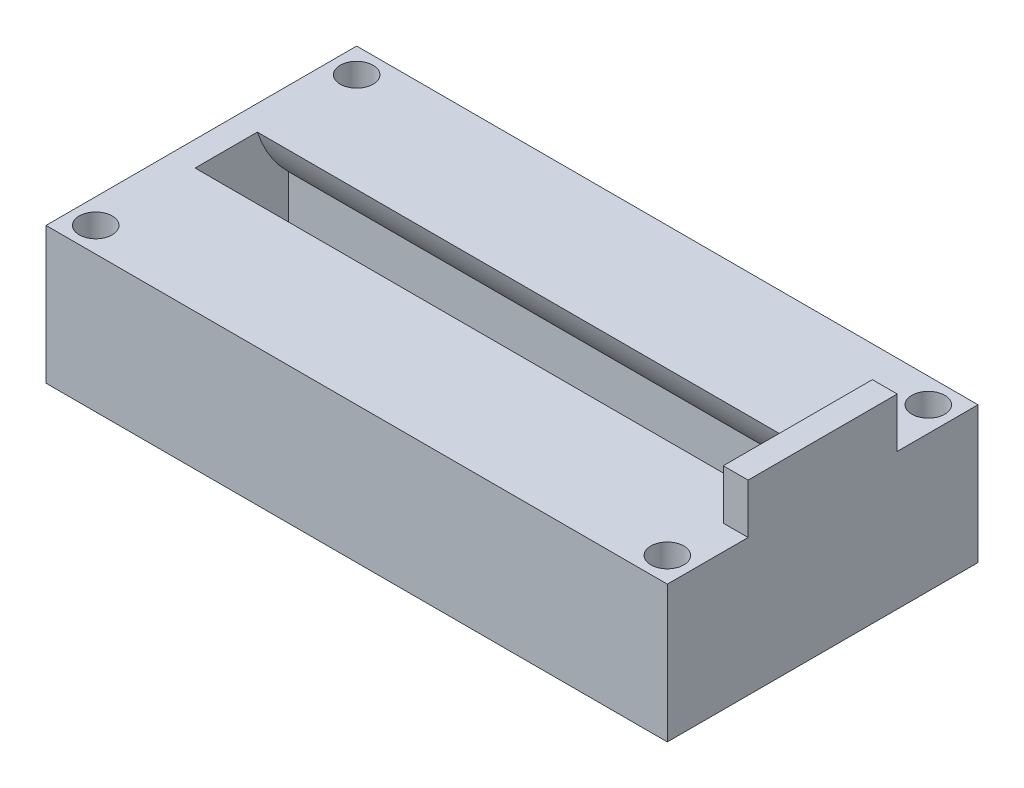
SolidWorks part; units mm, degrees
ref_plane "Front Plane" through (0, 0, 0) normal (0, 0, 1) x (1, 0, 0)
ref_plane "Top Plane" through (0, 0, 0) normal (0, 1, 0) x (1, 0, 0)
ref_plane "Right Plane" through (0, 0, 0) normal (1, 0, 0) x (0, 0, -1)
sketch "Sketch1" plane through (0, 0, 0) normal (0, 1, 0) x (1, 0, 0)
  line L0 (25, 22.1808) -> (25, 21.9237) construction
  line L1 (0, 0) -> (50, 0)
  line L2 (0, 0) -> (0, 25)
  line L4 (50, 0) -> (50, 25)
  line L8 (0, 25) -> (50, 25)
  line L18 (2, 17.5) -> (48, 17.5)
  line L19 (2, 17.5) -> (2, 7.5)
  line L20 (2, 7.5) -> (48, 7.5)
  line L21 (48, 17.5) -> (48, 7.5)
  circle A0 centre (2, 23) radius 1.325
  circle A1 centre (48, 23) radius 1.325
  circle A2 centre (48, 2) radius 1.325
  circle A3 centre (2, 2) radius 1.325
  point P5 (0, 0)
  dimension "D6" = 2.65
  dimension "D7" = 2.65
  dimension "D8" = 2.65
  dimension "D9" = 2.65
  dimension "D18" = 2
  dimension "D19" = 7.5
  dimension "D1" = 50
  dimension "D2" = 25
  dimension "D3" = 10
  dimension "D4" = 25
  dimension "D5" = 46
  dimension "D10" = 2
  dimension "D11" = 2
  dimension "D12" = 2
  dimension "D13" = 2
  dimension "D14" = 2
  dimension "D15" = 2
  dimension "D16" = 2
  dimension "D17" = 2
extrude "Boss-Extrude1" add sketch "Sketch1" along normal blind 7
sketch "Sketch2" plane through (0, 7, 0) normal (0, 1, 0) x (1, 0, 0)
  line L0 (0, 25) -> (0, 0)
  line L1 (0, 0) -> (50, 0)
  line L2 (50, 0) -> (50, 25)
  line L3 (50, 25) -> (0, 25)
  line L4 (48, 7.5) -> (48, 17.5) construction
  line L5 (2, 14.5) -> (48, 14.5)
  line L6 (2, 14.5) -> (2, 10.5)
  line L7 (2, 10.5) -> (48, 10.5)
  line L8 (48, 14.5) -> (48, 10.5)
  line L9 (2, 17.5) -> (2, 7.5) construction
  circle A0 centre (2, 23) radius 1.325
  circle A1 centre (48, 23) radius 1.325
  circle A2 centre (48, 2) radius 1.325
  circle A3 centre (2, 2) radius 1.325
  point P30 (-0.4995, 1.8011)
  dimension "D3" = 2.65
  dimension "D4" = 2.65
  dimension "D5" = 2.65
  dimension "D6" = 2.65
  dimension "D1" = 4
  dimension "D2" = 10.5
extrude "Boss-Extrude2" add sketch "Sketch2" along normal blind 4
sketch "Sketch3" plane through (0, 11, 0) normal (0, 1, 0) x (1, 0, 0)
  line L1 (48, 6.5) -> (50, 6.5)
  line L2 (48, 6.5) -> (48, 18.5)
  line L3 (48, 18.5) -> (50, 18.5)
  line L4 (50, 6.5) -> (50, 18.5)
  line L6 (50, 0) -> (50, 25) construction
  point P5 (0, 0)
  point P6 (0, 0)
  point P9 (0, 0)
  dimension "D1" = 12
  dimension "D2" = 6.5
  dimension "D3" = 2
  dimension "D4" = 2
extrude "Boss-Extrude3" add sketch "Sketch3" along normal blind 4
fillet "Fillet1" radius 10 1 edges at (25, 7, -14.5)
fillet "Fillet2" radius 10 1 edges at (25, 7, -10.5)
sketch "Sketch6" plane through (0, 0, 0) normal (0, -1, 0) x (-1, 0, 0)
  line L0 (-20.5, 21) -> (-29.5, 21) construction
  line L1 (-20.5, 19) -> (-29.5, 19)
  line L2 (-20.5, 23) -> (-29.5, 23)
  arc A0 (-20.5, 19) -> (-20.5, 23) centre (-20.5, 21) ccw
  arc A1 (-29.5, 23) -> (-29.5, 19) centre (-29.5, 21) ccw
  point P2 (-25, 21)
  dimension "D1" = 9
  dimension "D2" = 4
  dimension "D3" = 25
  dimension "D4" = 4
extrude "Cut-Extrude1" cut sketch "Sketch6" against normal blind 4
